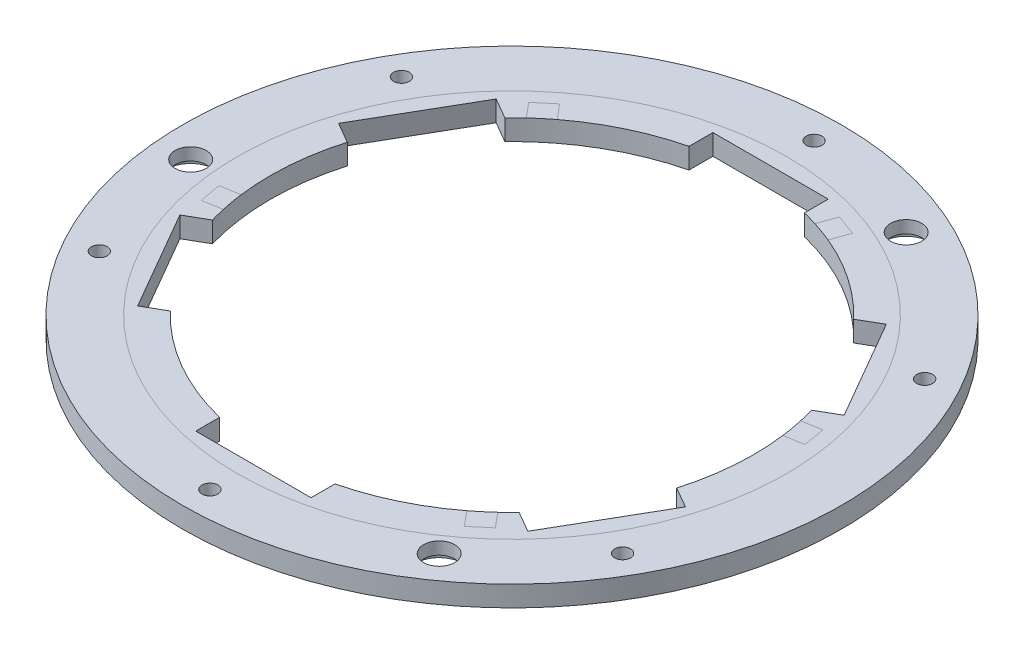
SolidWorks part; units mm, degrees
material "6061 Alloy"
ref_plane "Front Plane" through (0, 0, 0) normal (0, 0, 1) x (1, 0, 0)
ref_plane "Top Plane" through (0, 0, 0) normal (0, 1, 0) x (1, 0, 0)
ref_plane "Right Plane" through (0, 0, 0) normal (1, 0, 0) x (0, 0, -1)
sketch "Sketch1" plane through (0, 0, 0) normal (0, 1, 0) x (1, 0, 0)
  line L0 (-13.335, -54.2656) -> (-13.335, -58.1814)
  line L1 (13.335, -54.2656) -> (13.335, -58.1814)
  line L2 (-13.335, -59.7901) -> (13.335, -59.7901)
  line L3 (13.335, -58.1814) -> (13.335, -59.7901)
  line L4 (-13.335, -58.1814) -> (-13.335, -59.7901)
  line L5 (0, 0) -> (-68.319, -5.9771) construction
  line L6 (0, 0) -> (0, -23.1086) construction
  line L7 (0, 0) -> (17.8146, -65.9496) construction
  line L8 (0, 0) -> (27.4515, -55.5868) construction
  circle A0 centre (0, 0) radius 55.88
  circle A1 centre (0, 0) radius 76.2
  circle A2 centre (0, 0) radius 59.69
  circle A3 centre (0, -69.85) radius 1.8288
  circle A4 centre (-68.319, -5.9771) radius 3.5941
  dimension "D1" = 111.76
  dimension "D2" = 152.4
  dimension "D8" = 3.6576
  dimension "D11" = 7.1882
  dimension "D4" = 13.335
  dimension "D5" = 13.335
  dimension "D7" = 69.85
  dimension "D6" = 5.5245
  dimension "D9" = 68.58
  dimension "D10" = 85
  dimension "D13" = 17.8146
  dimension "D14" = 68.3133
  dimension "D16" = 61.9958
  dimension "D17" = 14.1512
  dimension "D3" = 3.81
extrude "Boss-Extrude1" add sketch "Sketch1" along normal blind 4.7625 contours L1 A2 L0 A0 | A1 A2 A0 region at (-15.0127, 0, 56.2235) region at (-74.0447, 0, 0)
pattern_circular "CirPattern1" count 6 over 360 about axis through (0, 4.7625, 0) along (0, 1, 0) of face at (-13.335, 2.3813, 57.0278) of face at (13.335, 2.3813, 57.0278) of face at (0, 4.7625, 71.6788) of face at (0, 2.3813, 59.7901)
sketch "Sketch2" plane through (0, 0, 0) normal (1, 0, 0) x (0, 0, -1)
  line L0 (76.2, 4.7625) -> (-76.2, 4.7625) construction
  line L1 (-76.2, 0) -> (76.2, 0) construction
  line L2 (76.2, 4.7625) -> (-76.2, 4.7625)
  line L3 (-76.2, 0) -> (76.2, 0)
  line L4 (0, 0) -> (0, 4.7625) construction
  circle A0 centre (-75.2856, 0) radius 2.667
  dimension "D1" = 5.334
  dimension "D2" = 0.9144
revolve "Cut-Revolve1" [suppressed] cut sketch "Sketch2" angle 360 about L4
sketch "Sketch4" plane through (0, 0, 0) normal (0, -1, 0) x (1, 0, 0)
  line L0 (0, 0) -> (-68.319, 5.9771) construction
  line L1 (0, 0) -> (0, -39.7137) construction
  circle A0 centre (-68.319, 5.9771) radius 5.588
  circle A2 centre (-68.319, 5.9771) radius 3.5941 construction
  circle A3 centre (-68.319, 5.9771) radius 3.5941
  dimension "D2" = 11.176
extrude "Cut-Extrude1" cut sketch "Sketch4" against normal blind 1.905 contours A0 region at (-73.749, 0, 5.9771)
pattern_circular "CirPattern2" count 3 over 360 about axis through (0, 0, 0) along (0, 1, 0) of face at (-68.319, 4.7625, 9.5712) of face at (-68.319, 1.905, 2.383) of face at (-68.319, 1.905, 0.3891)
sketch "Sketch5" plane through (0, 4.7625, 0) normal (0, 1, 0) x (1, 0, 0)
  line L0 (0, 0) -> (-20.0894, -55.1952)
  line L1 (0, 0) -> (0, -18.6852)
  line L2 (-16.5968, -53.0258) -> (-18.2257, -57.5011) construction
  line L3 (-18.2257, -57.5011) -> (-22.9993, -55.7636) construction
  line L4 (-22.9993, -55.7636) -> (-21.3704, -51.2884) construction
  line L5 (-59.7924, -7.9638) -> (-55.1022, -7.1368)
  line L6 (-54.2201, -12.1397) -> (-58.9103, -12.9667)
  line L7 (-58.9103, -12.9667) -> (-59.7924, -7.9638)
  line L8 (-36.7931, 47.7998) -> (-33.7318, 44.1515)
  line L9 (-37.6233, 40.8862) -> (-40.6846, 44.5345)
  line L10 (-40.6846, 44.5345) -> (-36.7931, 47.7998)
  line L11 (22.9993, 55.7636) -> (21.3704, 51.2884)
  line L12 (16.5968, 53.0258) -> (18.2257, 57.5011)
  line L13 (18.2257, 57.5011) -> (22.9993, 55.7636)
  line L14 (59.7924, 7.9638) -> (55.1022, 7.1368)
  line L15 (54.2201, 12.1397) -> (58.9103, 12.9667)
  line L16 (58.9103, 12.9667) -> (59.7924, 7.9638)
  line L17 (36.7931, -47.7998) -> (33.7318, -44.1515)
  line L18 (37.6233, -40.8862) -> (40.6846, -44.5345)
  line L19 (40.6846, -44.5345) -> (36.7931, -47.7998)
  circle A0 centre (0, 0) radius 55.5625
  circle A1 centre (0, 0) radius 58.7375 construction
  circle A2 centre (0, 0) radius 55.5625
  circle A3 centre (0, 0) radius 55.5625
  circle A4 centre (0, 0) radius 55.5625
  circle A5 centre (0, 0) radius 55.5625
  circle A6 centre (0, 0) radius 55.5625
  circle A7 centre (0, 0) radius 76.2
  circle A8 centre (0, 0) radius 63.5
  point P38 (0, 0)
  dimension "D1" = 111.125
  dimension "D3" = 20
  dimension "D4" = 2.54
  dimension "D5" = 4.7625
  dimension "D6" = 2.54
  dimension "D2" = 3.175
  dimension "D8" = 12.7
  dimension "D7" = 6
split line "Split Line1"
equation "\"Middle Coupler Inner Daimeter\"= 3.875in"
equation "\"Middle Coupler  Wall Thickness\" = 0.25in"
equation "\"Middle Coupler Bottom Thickness\"= 0.2in"
equation "\"Bearing Rail Offset\"= 0.45in"
equation "\"3-56 UNF Tap\"= 0.089in"
equation "\"3-56 UNF Clearance\"= 0.104in"
equation "\"Ball Bearing Distance\"= 0.03in"
equation "\"D1@Sketch1\"=\"Middle Coupler Inner Daimeter\"+0.5+0.0125*2in"
equation "\"TCA Outer Diameter\" = 6in"
equation "\"D2@Sketch1\"=\"TCA Outer Diameter\""
equation "\"D4@Sketch1\"=0.50 + (0.05/2)"
equation "\"D5@Sketch1\"=\"D4@Sketch1\""
equation "\"D7@Sketch1\"=(\"D2@Sketch1\"-0.5)/2"
equation "\"D8@Sketch1\"=\"6-32 Clearance\""
equation "\"D2@Sketch2\"=\"Interstage Aeroframe Wall Thickness\"/2"
equation "\"Interstage Aeroframe Wall Thickness\" = 0.072in"
equation "\"Compression Spring OD\"= 0.42in"
equation "\"10-24 Tap\"= 0.157in"
equation "\"10-24 Clearance\"= 0.196in"
equation "\"D2@Sketch4\"=\"Compression Spring OD\"+0.02"
equation "\"D3@Sketch1\"=0.125in+(0.05/2)"
equation "\"Lower Stage Fuselage Wall Thickness\" = 0.25in"
equation "\"6-32 Tap\" = 0.107in"
equation "\"1/4-20 Tap\" = 0.201in"
equation "\"3-48 Tap\"= 0.079in"
equation "\"12-24 Tap\" = 0.177in"
equation "\"3-48 Clearance\" = 0.104in"
equation "\"6-32 Clearance\" = 0.144"
equation "\"D6@Sketch1\"=3/16 + 0.03"
equation "\"D9@Sketch1\"=(\"D2@Sketch1\"+\"D1@Sketch1\")/4+0.1"
equation "\"D1@Sketch5\"=\"Middle Coupler Inner Daimeter\"+0.5"
equation "\"D5@Sketch5\"=3/16"
equation "\"D6@Sketch5\"=\"D4@Sketch5\""
equation "\"D1@Boss-Extrude1\"=3/16"
